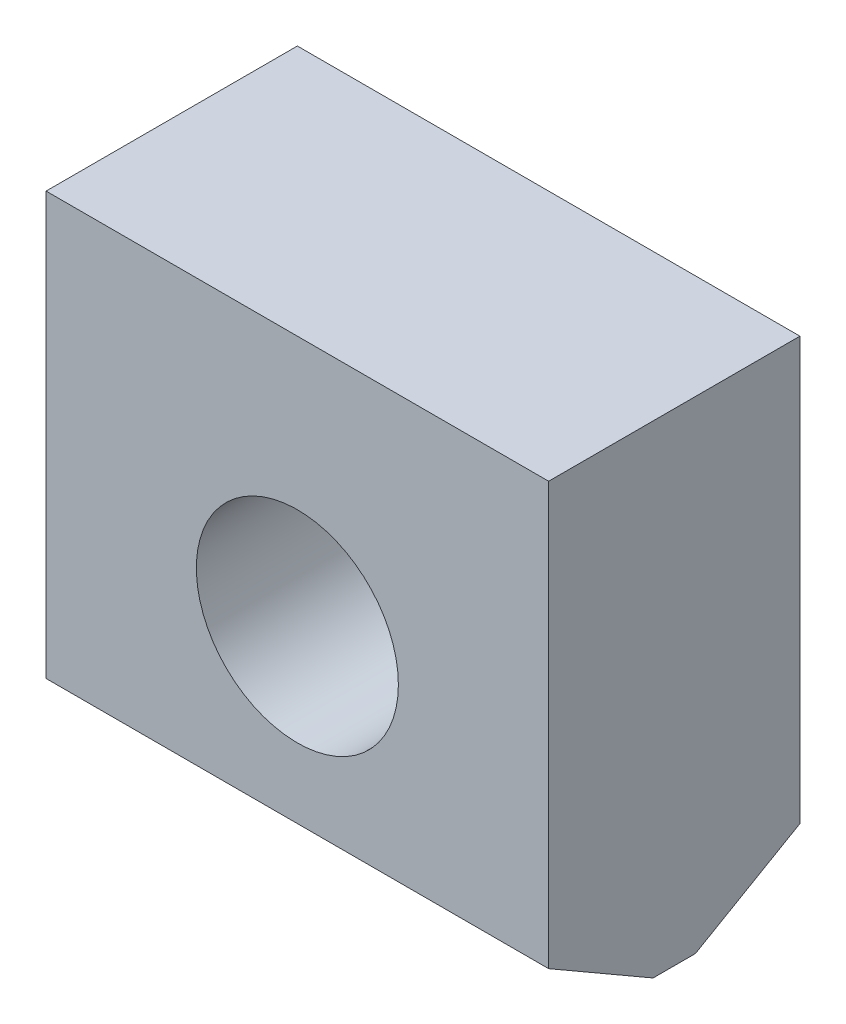
SolidWorks part; units mm, degrees
material "Простая углеродистая сталь"
ref_plane "Спереди" through (0, 0, 0) normal (0, 0, 1) x (1, 0, 0)
ref_plane "Сверху" through (0, 0, 0) normal (0, 1, 0) x (1, 0, 0)
ref_plane "Справа" through (0, 0, 0) normal (1, 0, 0) x (0, 0, -1)
sketch "Эскиз1" plane through (0, 0, 0) normal (0, 0, 1) x (1, 0, 0)
  line L1 (0, 0) -> (50, 0)
  line L2 (0, 0) -> (0, 48)
  line L3 (0, 48) -> (50, 48)
  line L4 (50, 0) -> (50, 48)
  point P5 (25, 48)
  dimension "D1" = 48
  dimension "D2" = 50
extrude "Бобышка-Вытянуть1" add sketch "Эскиз1" along normal blind 25
sketch "Эскиз2" plane through (0, 0, 25) normal (0, 0, 1) x (1, 0, 0)
  line L0 (0, 0) -> (50, 0) construction
  line L1 (50, 0) -> (50, 48) construction
  circle A0 centre (25, 23) radius 10.05
  dimension "D2" = 23
  dimension "D3" = 25
  dimension "D4" = 20.1
extrude "Вырез-Вытянуть1" cut sketch "Эскиз2" against normal through all
chamfer "Фаска1" distance 6 angle 60 1 edges at (25, 0, 0) first distance on face at (35.05, 23, 0)
chamfer "Фаска2" distance 6 angle 60 1 edges at (25, 0, 25) first distance on face at (35.05, 23, 25)
